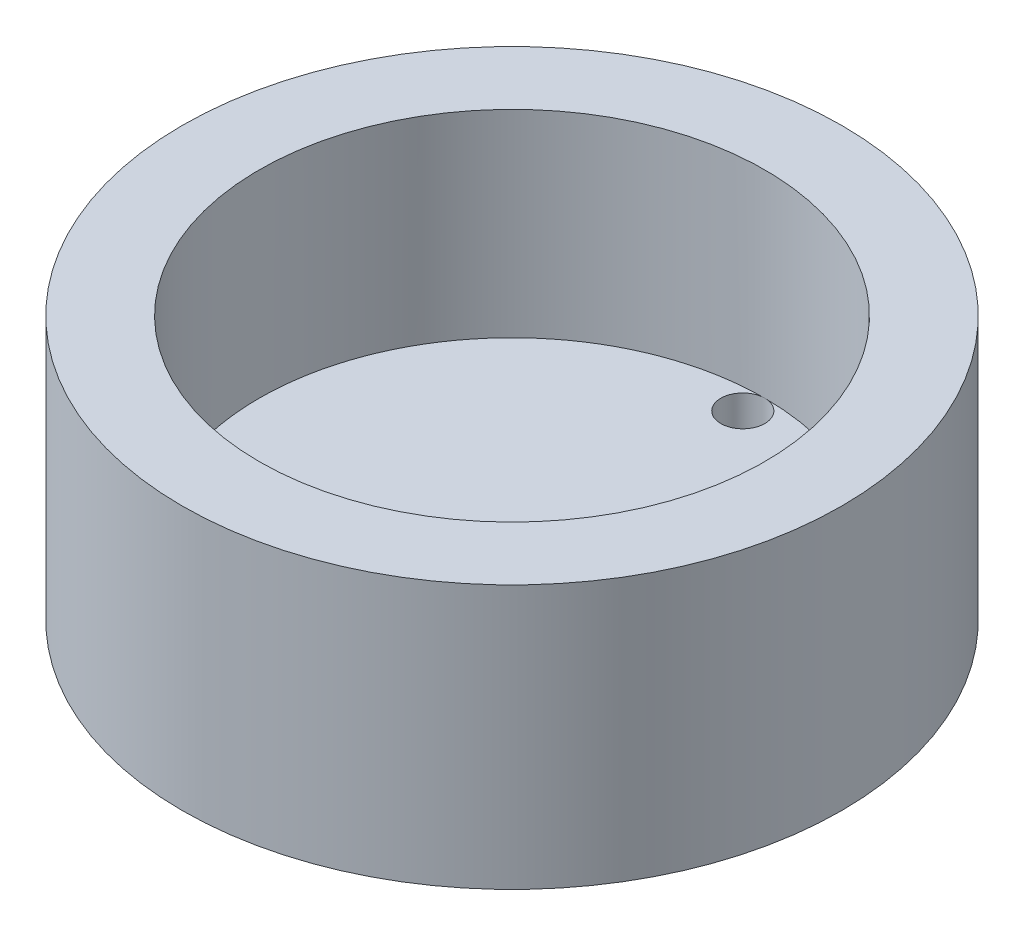
SolidWorks part; units mm, degrees
ref_plane "Front Plane" through (0, 0, 0) normal (0, 0, 1) x (1, 0, 0)
ref_plane "Top Plane" through (0, 0, 0) normal (0, 1, 0) x (1, 0, 0)
ref_plane "Right Plane" through (0, 0, 0) normal (1, 0, 0) x (0, 0, -1)
sketch "Sketch1" plane through (0, 0, 0) normal (0, 1, 0) x (1, 0, 0)
  circle A0 centre (0, 0) radius 30
  circle A1 centre (0, 0) radius 23
  dimension "D1" = 60
  dimension "D2" = 46
extrude "Boss-Extrude1" add sketch "Sketch1" along normal blind 24
extrude "Boss-Extrude2" add sketch "Sketch1<2>" along normal blind 6 contours A1 region at (0, 0, 0)
sketch "Sketch1<2>" plane through (0, 0, 0) normal (0, 1, 0) x (1, 0, 0) same geometry as "Sketch1"
sketch "Sketch2" plane through (0, 0, 0) normal (0, -1, 0) x (1, 0, 0)
  line L0 (-30, 0) -> (30, 0) construction
  circle A0 centre (0, 21) radius 2
  circle A1 centre (0, 0) radius 30 construction
  circle A2 centre (0, -21) radius 2
  point P9 (0, 0)
  point P11 (0, 9.6969)
  dimension "D1" = 4
  dimension "D2" = 21
extrude "Cut-Extrude1" cut sketch "Sketch2" against normal through all
